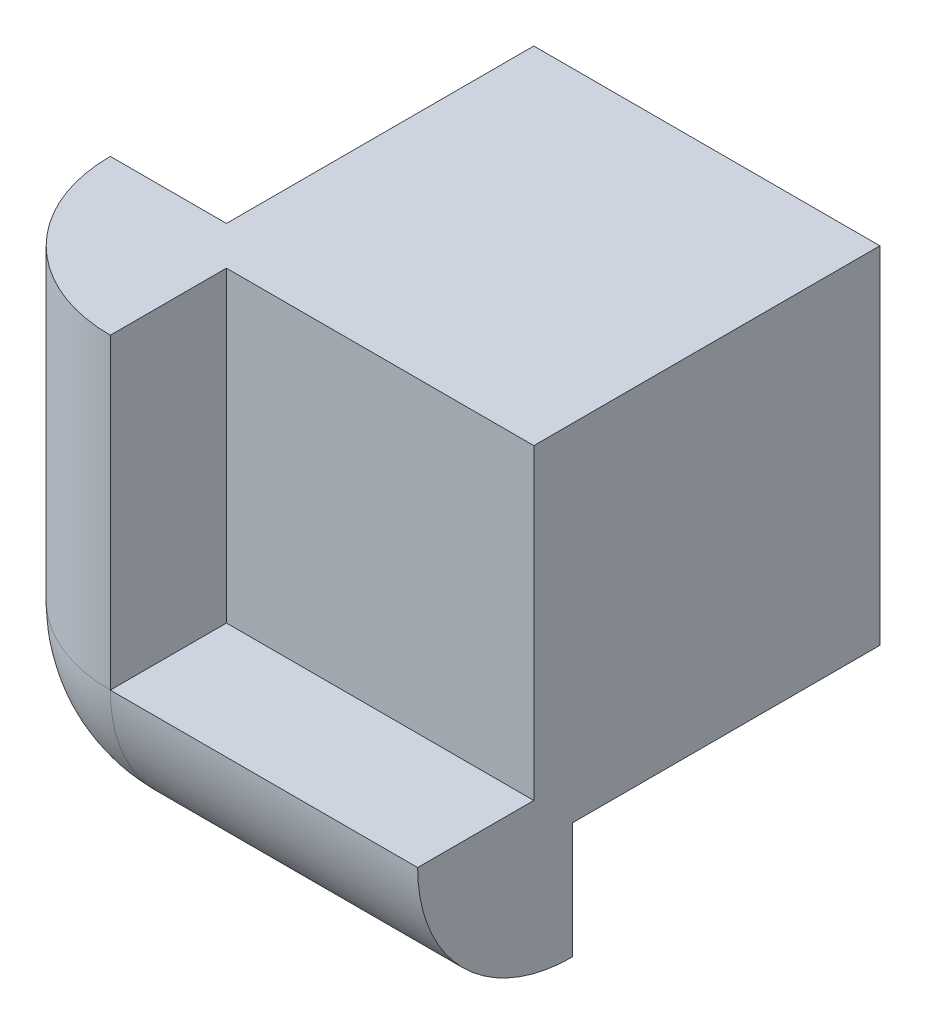
SolidWorks part; units mm, degrees
ref_plane "Front Plane" through (0, 0, 0) normal (0, 0, 1) x (1, 0, 0)
ref_plane "Top Plane" through (0, 0, 0) normal (0, 1, 0) x (1, 0, 0)
ref_plane "Right Plane" through (0, 0, 0) normal (1, 0, 0) x (0, 0, -1)
sketch "Sketch1" plane through (0, 0, 0) normal (0, 1, 0) x (1, 0, 0)
  line L0 (0, 1) -> (0, 0) construction
  line L5 (8.9375, 8.9375) -> (0, 8.9375)
  line L6 (8.9375, 8.9375) -> (8.9375, 0)
  line L7 (8.9375, 0) -> (1, 0)
  line L8 (0, 8.9375) -> (0, 1)
  line L9 (8.9375, 8.9375) -> (0, 0) construction
  line L10 (8.9375, 0) -> (0, 8.9375) construction
  line L11 (-3, -3) -> (1, -3)
  line L12 (-3, -3) -> (-3, 1)
  line L13 (-3, 1) -> (0, 1)
  line L14 (1, -3) -> (1, 0)
  line L15 (-3, -3) -> (1, 1) construction
  line L16 (-3, 1) -> (1, -3) construction
  line L17 (0, 1) -> (1, 1) construction
  line L18 (1, 0) -> (0, 0) construction
  line L19 (1, 0) -> (1, 1) construction
  point P0 (4.4687, 4.4687)
  point P7 (-1, -1)
  dimension "D1" = 1
  dimension "D2" = 4
  dimension "D3" = 8.9375
extrude "Boss-Extrude1" add sketch "Sketch1" along normal blind 8.9375
sketch "Sketch2" plane through (0, 0, 0) normal (0, 0, 1) x (1, 0, 0)
  line L0 (1, 8.9375) -> (1, 0) construction
  line L1 (-3, -3) -> (1, -3)
  line L2 (-3, -3) -> (-3, 1)
  line L3 (-3, 1) -> (1, 1)
  line L4 (1, -3) -> (1, 1)
  line L5 (-3, -3) -> (1, 1) construction
  line L6 (-3, 1) -> (1, -3) construction
  line L7 (-3, 8.9375) -> (-3, 0) construction
  point P0 (-1, -1)
extrude "Boss-Extrude4" add sketch "Sketch2" against normal up to surface (8.9375 mm away) up to face at (4.4687, 4.4687, -8.9375)
sketch "Sketch3" plane through (-3, 0, 0) normal (-1, 0, 0) x (0, 0, 1)
  line L0 (3, 8.9375) -> (3, 0) construction
  line L1 (-1, 1) -> (3, 1)
  line L2 (-1, 1) -> (-1, -3)
  line L3 (-1, -3) -> (3, -3)
  line L4 (3, 1) -> (3, -3)
extrude "Boss-Extrude5" add sketch "Sketch3" against normal up to vertex (11.9375 mm away) up to point (8.9375, 0, 0)
fillet "Fillet1" radius 4 3 edges at (-3, -3, -2.9687) (2.9687, -3, 3) (-3, 2.9687, 3)
sketch "Sketch4" plane through (0, 0, 0) normal (0, -1, 0) x (1, 0, 0)
  line L0 (1, -1) -> (8.9375, -8.9375) construction
  line L1 (1, -8.9375) -> (1, -1) construction
  line L2 (1, -1) -> (8.9375, -1) construction
  circle A0 centre (4.9687, -4.9687) radius 0.9
  dimension "D1" = 1.8
extrude "Cut-Extrude1" cut sketch "Sketch4" against normal blind 6
equation "\"corner_square\"=0.35187"
equation "\"D3@Sketch1\"=\"corner_square\""
equation "\"D1@Boss-Extrude1\"=\"corner_square\""
